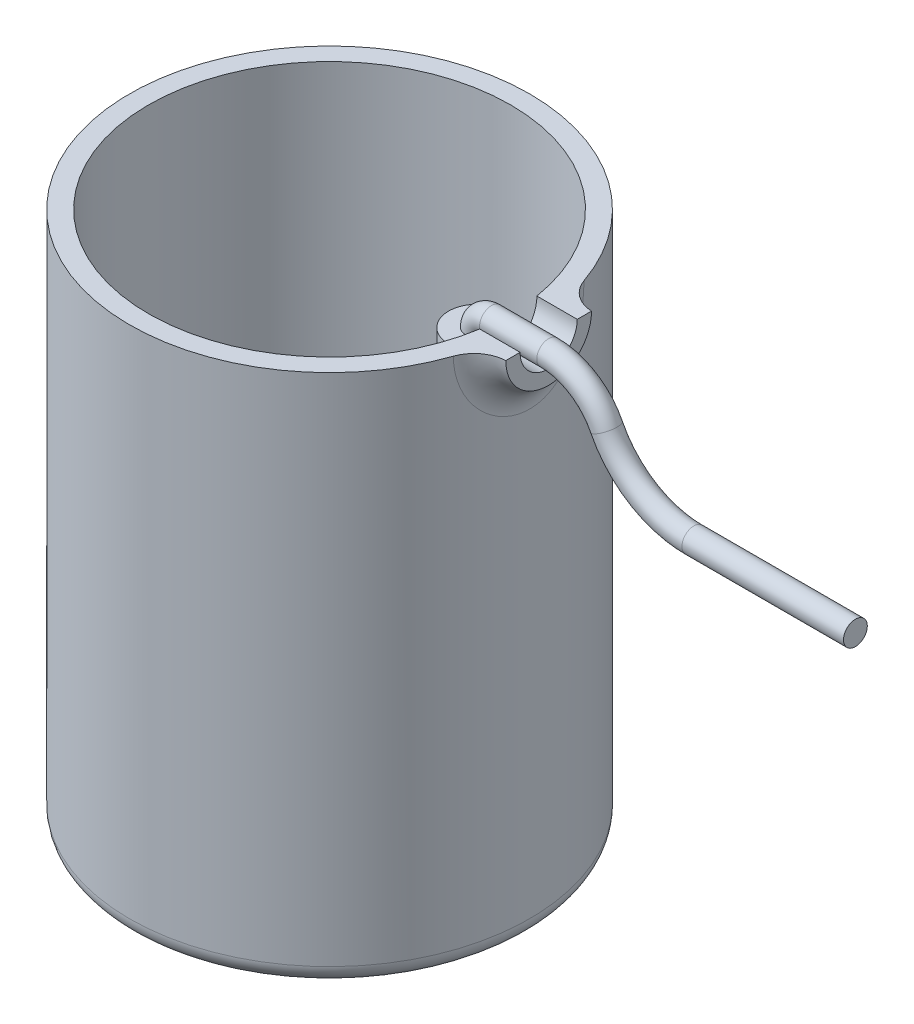
SolidWorks part; units mm, degrees
ref_plane "Front Plane" through (0, 0, 0) normal (0, 0, 1) x (1, 0, 0)
ref_plane "Top Plane" through (0, 0, 0) normal (0, 1, 0) x (1, 0, 0)
ref_plane "Right Plane" through (0, 0, 0) normal (1, 0, 0) x (0, 0, -1)
sketch "Sketch1" plane through (0, 0, 0) normal (0, 0, 1) x (1, 0, 0)
  line L0 (0, 0) -> (0, 52.5847) construction
  line L1 (0, 2) -> (19, 2)
  line L2 (19, 2) -> (19, 56)
  line L3 (19, 56) -> (21, 56)
  line L4 (21, 56) -> (21, 0)
  line L5 (21, 0) -> (0, 0)
  line L6 (0, 0) -> (0, 2)
  dimension "D1" = 42
  dimension "D2" = 56
  dimension "D3" = 2
  dimension "D4" = 2
revolve "Revolve1" add sketch "Sketch1" angle 360 about L0
fillet "Fillet1" radius 2 1 edges at (0, 0, -21)
sketch "Sketch2" plane through (0, 0, 0) normal (0, 0, 1) x (1, 0, 0)
  line L0 (21, 56) -> (19, 56) construction
  line L1 (19, 56) -> (-19, 56) construction
  line L2 (19, 53) -> (23, 53)
  line L3 (23, 53) -> (23, 51.5)
  line L4 (23, 51.5) -> (19, 51.5)
  line L5 (19, 51.5) -> (19, 53)
  dimension "D1" = 1.5
  dimension "D2" = 4
  dimension "D3" = 3
revolve "Revolve2" add sketch "Sketch2" angle 180 mid plane about L0
sketch "Sketch3" plane through (23, 0, 0) normal (1, 0, 0) x (0, 0, -1)
  circle A0 centre (0, 56) radius 3
  arc A1 (-3, 56) -> (3, 56) centre (0, 56) ccw construction
extrude "Cut-Extrude1" cut sketch "Sketch3" against normal up to next
sketch "Sketch4" plane through (0, 2, 0) normal (0, 1, 0) x (1, 0, 0)
  circle A0 centre (15.5, 0) radius 3
  circle A2 centre (0, 0) radius 19 construction
  dimension "D1" = 6
  dimension "D2" = 15.5
extrude "Boss-Extrude2" add sketch "Sketch4" along normal blind 51
sketch "Sketch5" plane through (0, 0, 0) normal (0, 0, 1) x (1, 0, 0)
  line L0 (18.5, 53) -> (12.5, 53) construction
  line L1 (17, 54.5) -> (23, 54.5)
  line L3 (38.2394, 45.0887) -> (55.1984, 45.0887)
  line L4 (23, 53) -> (23, 56) construction
  arc A0 (15.5, 53) -> (17, 54.5) centre (17, 53) cw
  arc A1 (23, 54.5) -> (29.0788, 50.746) centre (23, 47.7013) cw
  arc A2 (29.0788, 50.746) -> (38.2394, 45.0887) centre (38.2394, 55.3341) ccw
  point P21 (23, 54.5)
sketch "Sketch6" plane through (0, 53, 0) normal (0, 1, 0) x (1, 0, 0)
  line L0 (15.5, 0) -> (17, 0) construction
  circle A0 centre (15.5, 0) radius 1.25
  dimension "D1" = 2.5
sweep "Sweep1" add profiles "Sketch6" path "Sketch5"
fillet "Fillet2" radius 3.5 1 edges at (20.9947, 51.5248, 0.4719)
